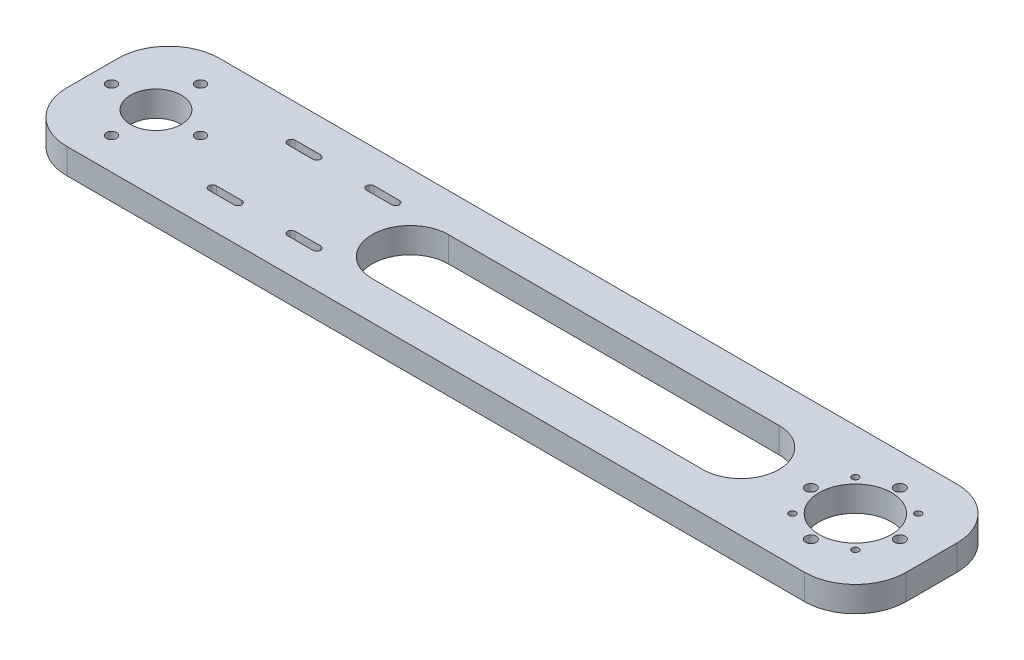
SolidWorks part; units mm, degrees
ref_plane "前视基准面" through (0, 0, 0) normal (0, 0, 1) x (1, 0, 0)
ref_plane "上视基准面" through (0, 0, 0) normal (0, 1, 0) x (1, 0, 0)
ref_plane "右视基准面" through (0, 0, 0) normal (1, 0, 0) x (0, 0, -1)
other "Configuration Table"
sketch "草图1" plane through (0, 0, 0) normal (0, 1, 0) x (1, 0, 0)
  line L1 (-165, -30) -> (165, -30)
  line L2 (-165, -30) -> (-165, 30)
  line L3 (-165, 30) -> (165, 30)
  line L4 (165, -30) -> (165, 30)
  line L5 (-165, -30) -> (165, 30) construction
  line L6 (-165, 30) -> (165, -30) construction
  point P0 (0, 0)
  dimension "D1" = 330
  dimension "D2" = 60
extrude "凸台-拉伸1" add sketch "草图1" along normal blind 10
fillet "圆角1" radius 20 4 edges at (-165, 5, -30) (-165, 5, 30) (165, 5, -30) (165, 5, 30)
sketch "草图5" plane through (0, 0, 0) normal (0, -1, 0) x (1, 0, 0)
  line L1 (-145, 30) -> (145, 30) construction
  line L2 (-165, -10) -> (-165, 10) construction
  circle A0 centre (-140, 0) radius 10
  dimension "D1" = 20
  dimension "D2" = 30
  dimension "D3" = 25
extrude "切除-拉伸3" cut sketch "草图5" against normal blind 10
sketch "草图15" plane through (0, 0, 0) normal (0, -1, 0) x (1, 0, 0)
  line L0 (165, 10) -> (165, -10) construction
  line L1 (-145, 30) -> (145, 30) construction
  circle A0 centre (135, 0) radius 14.25
  dimension "D1" = 30
  dimension "D2" = 30
  dimension "D3" = 28.5
extrude "切除-拉伸12" cut sketch "草图15" against normal through all
sketch "草图18" plane through (0, 0, 0) normal (0, -1, 0) x (1, 0, 0)
  circle A0 centre (122.6256, 12.3744) radius 1.3
  circle A1 centre (147.3744, 12.3744) radius 1.3
  circle A2 centre (147.3744, -12.3744) radius 1.3
  circle A3 centre (122.6256, -12.3744) radius 1.3
  dimension "D1" = 2.6
  dimension "D2" = 2.6
  dimension "D3" = 2.6
  dimension "D4" = 2.6
extrude "切除-拉伸14" cut sketch "草图18" against normal through all
cosmetic thread "装饰螺纹线5" parameters "D2"=3.6
cosmetic thread "装饰螺纹线6" parameters "D2"=3.6
cosmetic thread "装饰螺纹线7" parameters "D2"=3.6
cosmetic thread "装饰螺纹线8" parameters "D2"=3.6
sketch "草图19" plane through (0, 0, 0) normal (0, -1, 0) x (-1, 0, 0)
  line L0 (102.2654, -15.5) -> (92.2654, -15.5) construction
  line L3 (165, 0) -> (-165, 0) construction
  line L4 (165, 10) -> (165, -10) construction
  line L5 (-165, -10) -> (-165, 10) construction
  line L6 (102.2654, 15.5) -> (92.2654, 15.5) construction
  line L7 (102.2654, 17) -> (92.2654, 17)
  line L8 (102.2654, 14) -> (92.2654, 14)
  line L9 (71.2654, -15.5) -> (61.2654, -15.5) construction
  line L10 (71.2654, -17) -> (61.2654, -17)
  line L11 (71.2654, -14) -> (61.2654, -14)
  line L12 (71.2654, 15.5) -> (61.2654, 15.5) construction
  line L13 (71.2654, 17) -> (61.2654, 17)
  line L14 (71.2654, 14) -> (61.2654, 14)
  line L15 (102.2654, -17) -> (92.2654, -17)
  line L16 (102.2654, -14) -> (92.2654, -14)
  arc A2 (102.2654, 17) -> (102.2654, 14) centre (102.2654, 15.5) cw
  arc A3 (92.2654, 14) -> (92.2654, 17) centre (92.2654, 15.5) cw
  arc A4 (71.2654, -17) -> (71.2654, -14) centre (71.2654, -15.5) ccw
  arc A5 (61.2654, -14) -> (61.2654, -17) centre (61.2654, -15.5) ccw
  arc A6 (71.2654, 17) -> (71.2654, 14) centre (71.2654, 15.5) cw
  arc A7 (61.2654, 14) -> (61.2654, 17) centre (61.2654, 15.5) cw
  arc A8 (102.2654, -17) -> (102.2654, -14) centre (102.2654, -15.5) ccw
  arc A9 (92.2654, -14) -> (92.2654, -17) centre (92.2654, -15.5) ccw
  point P2 (97.2654, -15.5)
  point P17 (97.2654, 15.5)
  point P24 (66.2654, -15.5)
  point P31 (66.2654, 15.5)
  dimension "D4" = 10
  dimension "D3" = 3
extrude "切除-拉伸15" cut sketch "草图19" against normal through all
sketch "草图20" plane through (0, 10, 0) normal (0, 1, 0) x (1, 0, 0)
  line L0 (-140, 10) -> (-140, -10) construction
  line L1 (-150, 0) -> (-130, 0) construction
  circle A4 centre (-140, 0) radius 10 construction
  circle A5 centre (-140, 0) radius 17.5 construction
  circle A6 centre (-140, 17.5) radius 2
  dimension "D1" = 4
extrude "切除-拉伸16" cut sketch "草图20" against normal blind 10
sketch "草图21" plane through (0, 0, 0) normal (0, -1, 0) x (1, 0, 0)
  circle A0 centre (135, 0) radius 17.5
  circle A1 centre (135, 17.5) radius 2.1
  circle A2 centre (152.5, 0) radius 2.1
  circle A3 centre (135, -17.5) radius 2.1
  circle A4 centre (117.5, 0) radius 2.1
  dimension "D1" = 35
  dimension "D2" = 4.2
  dimension "D3" = 4.2
  dimension "D4" = 4.2
  dimension "D5" = 4.2
extrude "切除-拉伸17" cut sketch "草图21" against normal blind 10 contours A0 A1 | A0 A1 | A0 A2 | A0 A2 | A0 A3 | A0 A4 | A0 A4 | A3 region at (151.5864, 0, 0) region at (153.3682, 0, 0) region at (135, 0, 16.5864) region at (135, 0, 18.3682) region at (135, 0, -16.5864) region at (118.4136, 0, 0) region at (116.6318, 0, 0)
cosmetic thread "装饰螺纹线1" parameters "D2"=5.2
cosmetic thread "装饰螺纹线2" parameters "D2"=5.2
cosmetic thread "装饰螺纹线3" parameters "D2"=5.2
cosmetic thread "装饰螺纹线4" parameters "D2"=5.2
sketch "草图22" plane through (0, 10, 0) normal (0, 1, 0) x (1, 0, 0)
  line L0 (-40, 0) -> (90, 0) construction
  line L1 (-40, 15) -> (90, 15)
  line L2 (-40, -15) -> (90, -15)
  line L3 (145, 30) -> (-145, 30) construction
  line L4 (165, -10) -> (165, 10) construction
  arc A0 (-40, 15) -> (-40, -15) centre (-40, 0) ccw
  arc A1 (90, -15) -> (90, 15) centre (90, 0) ccw
  point P2 (25, 0)
  dimension "D3" = 140
  dimension "D1" = 130
  dimension "D2" = 15
extrude "切除-拉伸18" cut sketch "草图22" against normal through all
pattern_circular "阵列(圆周)1" count 4 every 90 about axis through (-140, 10, 0) along (0, -1, 0) of "切除-拉伸16"
